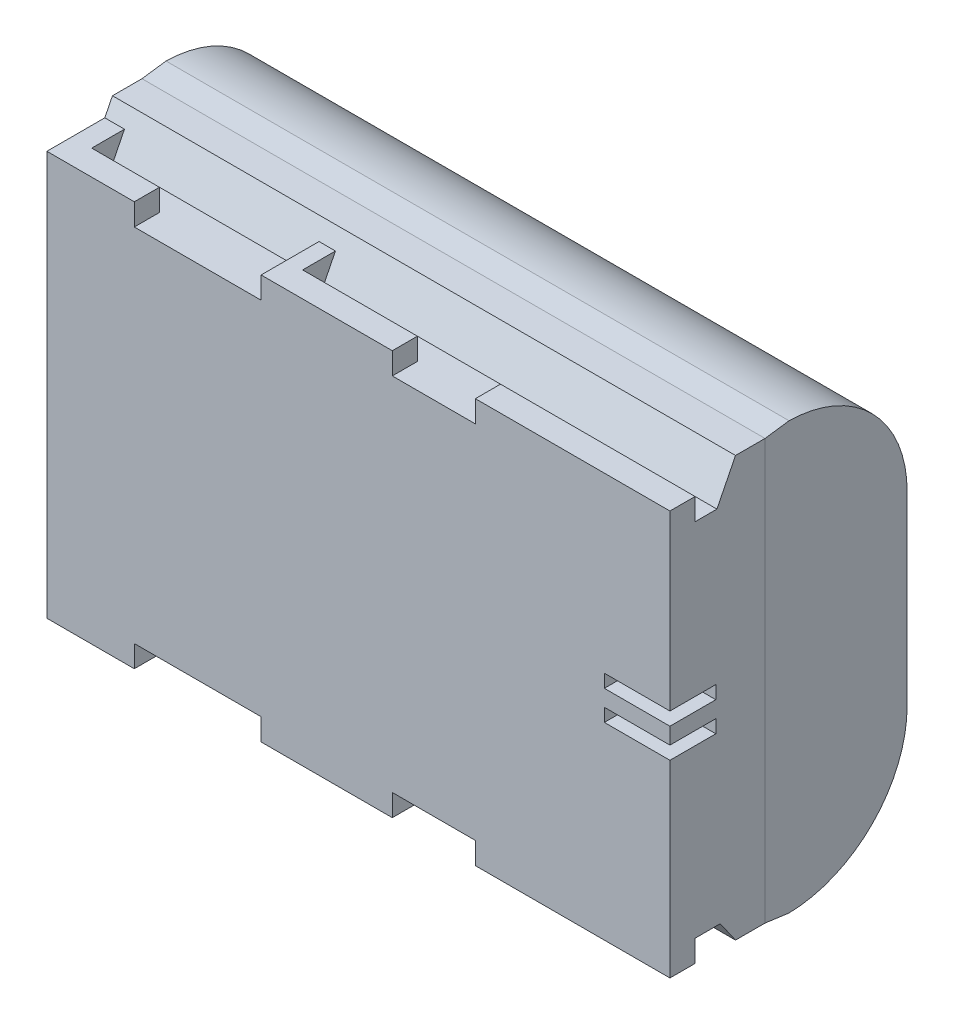
SolidWorks part; units mm, degrees
ref_plane "Спереди" through (0, 0, 0) normal (0, 0, 1) x (1, 0, 0)
ref_plane "Сверху" through (0, 0, 0) normal (0, 1, 0) x (1, 0, 0)
ref_plane "Справа" through (0, 0, 0) normal (1, 0, 0) x (0, 0, -1)
sketch "Эскиз1" plane through (0, 0, 0) normal (0, 0, 1) x (1, 0, 0)
  line L1 (0, 0) -> (57, 0)
  line L2 (0, 0) -> (0, 38.4)
  line L3 (0, 38.4) -> (57, 38.4)
  line L4 (57, 0) -> (57, 38.4)
  dimension "D1" = 57
  dimension "D2" = 38.4
extrude "Бобышка-Вытянуть1" add sketch "Эскиз1" along normal blind 8.7
sketch "Эскиз2" plane through (0, 0, 8.7) normal (0, 0, 1) x (1, 0, 0)
  line L0 (57, 0) -> (57, 38.4) construction
  line L1 (0, 38.4) -> (57, 38.4)
  line L2 (0, 38.4) -> (0, 37)
  line L3 (0, 37) -> (57, 37)
  line L4 (57, 38.4) -> (57, 37)
  line L5 (0, 0) -> (57, 0) construction
  dimension "D1" = 37
extrude "Вырез-Вытянуть1" cut sketch "Эскиз2" against normal blind 2.3
sketch "Эскиз3" plane through (0, 0, 0) normal (0, 1, 0) x (1, 0, 0)
  line L0 (57, -6.4) -> (57, 0) construction
  line L1 (0, -6.4) -> (57, -6.4)
  line L2 (0, -6.4) -> (0, -4.1)
  line L3 (0, -4.1) -> (57, -4.1)
  line L4 (57, -6.4) -> (57, -4.1)
  dimension "D1" = 2.3
extrude "Вырез-Вытянуть2" cut sketch "Эскиз3" along normal blind 2
sketch "Эскиз4" plane through (0, 0, 8.7) normal (0, 0, 1) x (1, 0, 0)
  line L0 (0, 0) -> (57, 0) construction
  line L1 (8, 0) -> (19.6, 0)
  line L2 (8, 0) -> (8, 2)
  line L3 (8, 2) -> (19.6, 2)
  line L4 (19.6, 0) -> (19.6, 2)
  line L5 (0, 2) -> (57, 2) construction
  line L6 (31.6, 0) -> (39.2, 0)
  line L7 (31.6, 0) -> (31.6, 2)
  line L8 (31.6, 2) -> (39.2, 2)
  line L9 (39.2, 0) -> (39.2, 2)
  line L10 (0, 37) -> (0, 0) construction
  line L11 (0, 18.5) -> (28.0003, 18.5) construction
  line L12 (39.2, 37) -> (39.2, 35)
  line L13 (31.6, 35) -> (39.2, 35)
  line L14 (31.6, 37) -> (31.6, 35)
  line L15 (31.6, 37) -> (39.2, 37)
  line L16 (19.6, 37) -> (19.6, 35)
  line L17 (8, 35) -> (19.6, 35)
  line L18 (8, 37) -> (8, 35)
  line L19 (8, 37) -> (19.6, 37)
  dimension "D1" = 8
  dimension "D2" = 11.6
  dimension "D3" = 12
  dimension "D4" = 7.6
extrude "Вырез-Вытянуть3" cut sketch "Эскиз4" against normal up to surface (2.3 mm away) up to face at (28.5, 1, 6.4)
sketch "Эскиз5" plane through (57, 0, 0) normal (1, 0, 0) x (0, 0, -1)
  line L0 (-4.1, 0) -> (-4.1, 2)
  line L1 (-4.1, 2) -> (-2.7, 0)
  line L2 (-4.1, 0) -> (0, 0) construction
  line L3 (-2.7, 0) -> (-4.1, 0)
  line L4 (-8.7, 0) -> (-8.7, 37) construction
  line L5 (0, 19.2) -> (-12.3399, 19.2) construction
  line L6 (0, 0) -> (0, 38.4) construction
  line L7 (-2.7, 0) -> (-2.7, 42.4842) construction
  line L8 (-4.4, 35) -> (-2.7, 38.4)
  line L9 (-6.4, 37) -> (-6.4, 35)
  line L10 (-6.4, 35) -> (-4.4, 35)
  line L11 (-2.7, 38.4) -> (-6.4, 38.4)
  line L12 (-6.4, 38.4) -> (-6.4, 37)
  line L13 (-6.4, 38.4) -> (0, 38.4) construction
  dimension "D1" = 6
  dimension "D2" = 2
  dimension "D3" = 2
extrude "Вырез-Вытянуть4" cut sketch "Эскиз5" against normal through all
sketch "Эскиз6" plane through (0, 0, 0) normal (0, -1, 0) x (1, 0, 0)
  line L1 (19.6, 6.4) -> (21.1, 6.4)
  line L2 (19.6, 6.4) -> (19.6, 2.7)
  line L3 (19.6, 2.7) -> (21.1, 2.7)
  line L4 (21.1, 6.4) -> (21.1, 2.7)
  line L5 (0, 2.7) -> (57, 2.7) construction
  line L6 (0, 6.4) -> (1.8, 6.4)
  line L7 (0, 6.4) -> (0, 2.7)
  line L8 (0, 2.7) -> (1.8, 2.7)
  line L9 (1.8, 6.4) -> (1.8, 2.7)
  dimension "D1" = 1.5
  dimension "D2" = 1.8
extrude "Бобышка-Вытянуть2" add sketch "Эскиз6" against normal blind 2
sketch "Эскиз7" plane through (0, 37, 0) normal (0, 1, 0) x (1, 0, 0)
  line L0 (0, -2.7) -> (57, -2.7) construction
  line L1 (0, -6.4) -> (1.8, -6.4)
  line L2 (0, -6.4) -> (0, -2.7)
  line L3 (0, -2.7) -> (1.8, -2.7)
  line L4 (1.8, -6.4) -> (1.8, -2.7)
  line L6 (19.6, -6.4) -> (21.1, -6.4)
  line L7 (19.6, -6.4) -> (19.6, -2.7)
  line L8 (19.6, -2.7) -> (21.1, -2.7)
  line L9 (21.1, -6.4) -> (21.1, -2.7)
  dimension "D1" = 1.8
  dimension "D2" = 1.5
extrude "Бобышка-Вытянуть3" add sketch "Эскиз7" against normal blind 2
ref_plane "Плоскость1" through (0, 19.2, 0) normal (0, -1, 0) x (-1, 0, 0)
sketch "Эскиз10" plane through (0, 0, 8.7) normal (0, 0, 1) x (1, 0, 0)
  line L0 (57, 19.2) -> (48.8382, 19.2) construction
  line L1 (57, 0) -> (57, 37) construction
  line L2 (57, 21.15) -> (57, 19.95)
  line L3 (51, 16.5) -> (57, 16.5) construction
  line L4 (51, 16.5) -> (51, 21.9) construction
  line L5 (51, 21.9) -> (57, 21.9) construction
  line L6 (57, 16.5) -> (57, 21.9) construction
  line L7 (51, 16.5) -> (57, 21.9) construction
  line L8 (51, 21.9) -> (57, 16.5) construction
  line L9 (51, 17.25) -> (57, 17.25)
  line L10 (51, 17.25) -> (51, 18.45)
  line L11 (51, 18.45) -> (57, 18.45)
  line L12 (57, 17.25) -> (57, 18.45)
  line L13 (51, 19.95) -> (57, 19.95)
  line L14 (51, 21.15) -> (51, 19.95)
  line L15 (51, 21.15) -> (57, 21.15)
  line L16 (-4.785, 19.2) -> (4.785, 19.2) construction
  point P4 (54, 19.2)
  dimension "D1" = 5.4
  dimension "D2" = 6
  dimension "D3" = 1.2
  dimension "D4" = 0.75
extrude "Вырез-Вытянуть5" cut sketch "Эскиз10" against normal blind 4.2
sketch "Эскиз11" plane through (0, 0, 0) normal (-1, 0, 0) x (0, 0, 1)
  line L0 (0, 0) -> (-2.2, -0.3)
  line L1 (0, 38.4) -> (-2.2, 38.7)
  line L2 (-13, -0.3) -> (-13, 38.7)
  line L3 (0, 38.4) -> (0, 0) construction
  line L4 (-13, -0.3) -> (-2.2, -0.3)
  line L5 (-13, 38.7) -> (-2.2, 38.7)
  line L6 (0, 38.4) -> (0, 0)
  point P10 (0, 19.2)
  dimension "D1" = 2.2
  dimension "D2" = 13
  dimension "D3" = 39
  dimension "D4" = 19.5
extrude "Бобышка-Вытянуть4" add sketch "Эскиз11" against normal up to surface (57 mm away) separate body up to face at (57, 18.92, 5.485)
fillet "Скругление1" radius 11 2 edges at (28.5, 38.7, -13) (28.5, -0.3, -13)
